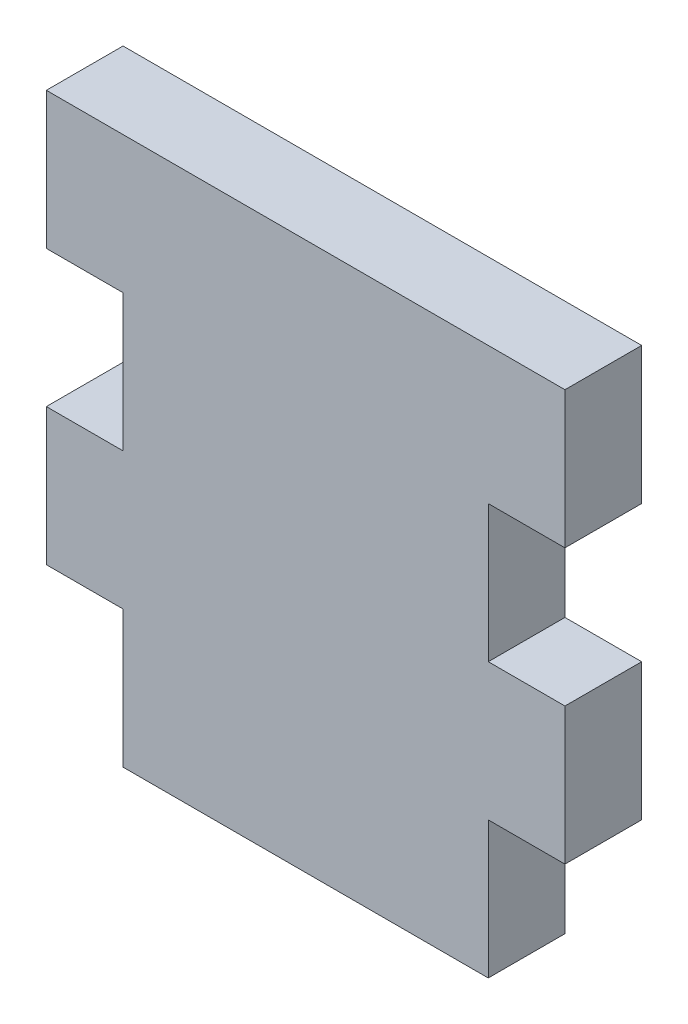
SolidWorks part; units mm, degrees
ref_plane "Front Plane" through (0, 0, 0) normal (0, 0, 1) x (1, 0, 0)
ref_plane "Top Plane" through (0, 0, 0) normal (0, 1, 0) x (1, 0, 0)
ref_plane "Right Plane" through (0, 0, 0) normal (1, 0, 0) x (0, 0, -1)
sketch "Sketch1" plane through (0, 0, 0) normal (0, 0, 1) x (1, 0, 0)
  line L1 (-88.0852, 14.1109) -> (-52.0172, 14.1109)
  line L2 (-88.0852, 14.1109) -> (-88.0852, -23.9891)
  line L3 (-88.0852, -23.9891) -> (-52.0172, -23.9891)
  line L4 (-52.0172, 14.1109) -> (-52.0172, -23.9891)
  dimension "D1" = 38.1
  dimension "D2" = 36.068
extrude "Boss-Extrude1" add sketch "Sketch1" along normal blind 5.334
sketch "Sketch2" plane through (0, 0, 5.334) normal (0, 0, 1) x (1, 0, 0)
  line L0 (-88.0852, 14.1109) -> (-88.0852, -23.9891) construction
  line L1 (-88.0852, -23.9891) -> (-82.7512, -23.9891)
  line L2 (-88.0852, -23.9891) -> (-88.0852, -14.4641)
  line L3 (-88.0852, -14.4641) -> (-82.7512, -14.4641)
  line L4 (-82.7512, -23.9891) -> (-82.7512, -14.4641)
  line L5 (-88.0852, -4.9391) -> (-82.7512, -4.9391)
  line L6 (-88.0852, -4.9391) -> (-88.0852, 4.5859)
  line L7 (-88.0852, 4.5859) -> (-82.7512, 4.5859)
  line L8 (-82.7512, -4.9391) -> (-82.7512, 4.5859)
  line L9 (-82.7512, 4.5859) -> (-82.7512, 14.1109) construction
  line L10 (-52.0172, 14.1109) -> (-88.0852, 14.1109) construction
  line L11 (-82.7512, -4.9391) -> (-82.7512, -14.4641) construction
  line L12 (-70.0512, 14.1109) -> (-70.0512, -23.9891) construction
  line L13 (-88.0852, -23.9891) -> (-52.0172, -23.9891) construction
  line L14 (-57.3512, -4.9391) -> (-57.3512, -14.4641) construction
  line L15 (-57.3512, 4.5859) -> (-57.3512, 14.1109) construction
  line L16 (-57.3512, -4.9391) -> (-57.3512, 4.5859)
  line L17 (-52.0172, 4.5859) -> (-57.3512, 4.5859)
  line L18 (-52.0172, -4.9391) -> (-52.0172, 4.5859)
  line L19 (-52.0172, -4.9391) -> (-57.3512, -4.9391)
  line L20 (-57.3512, -23.9891) -> (-57.3512, -14.4641)
  line L21 (-52.0172, -14.4641) -> (-57.3512, -14.4641)
  line L22 (-52.0172, -23.9891) -> (-52.0172, -14.4641)
  line L23 (-52.0172, -23.9891) -> (-57.3512, -23.9891)
  dimension "D1" = 5.334
extrude "Cut-Extrude1" cut sketch "Sketch2" against normal through all
equation "\"MDF\" = .21"
equation "\"Foamcore\"= .13in"
equation "\"Gmaterial\"= \"MDF\""
equation "\"D1@Boss-Extrude1\"=\"MDF\""
equation "\"D1@Sketch2\"=\"MDF\""
equation "\"D2@Sketch1\"=\"MDF\"+\"MDF\"+1"
